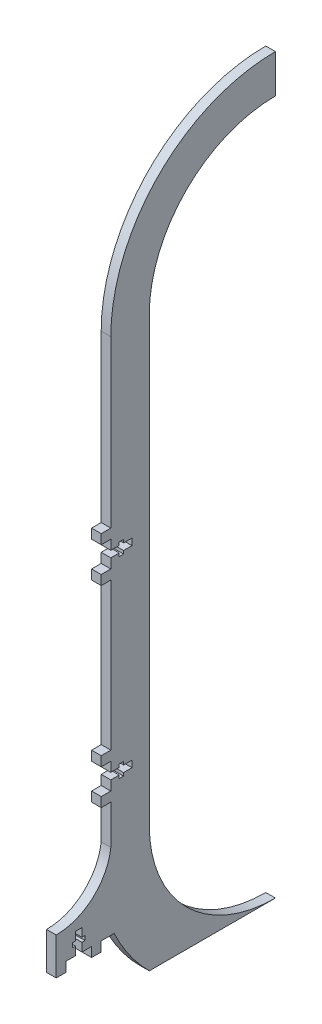
SolidWorks part; units mm, degrees
ref_plane "Front Plane" through (0, 0, 0) normal (0, 0, 1) x (1, 0, 0)
ref_plane "Top Plane" through (0, 0, 0) normal (0, 1, 0) x (1, 0, 0)
ref_plane "Right Plane" through (0, 0, 0) normal (1, 0, 0) x (0, 0, -1)
sketch "Elevator Ball Support Rail" plane through (0, 0, 0) normal (1, 0, 0) x (0, 0, -1)
  line L0 (83.312, 229.362) -> (83.312, 254.762)
  line L1 (-31.75, -120.142) -> (-25.4, -120.142)
  line L2 (83.312, -229.362) -> (0, -229.362)
  line L3 (-31.75, -196.342) -> (-23.2361, -196.342)
  line L6 (0, 146.05) -> (0, -146.05)
  line L7 (-25.4, -146.05) -> (-25.4, -196.342) construction
  line L8 (0, -146.05) -> (0, -229.362) construction
  line L12 (-61.468, -178.0893) -> (-61.468, -196.342)
  line L42 (0, 0) -> (-25.4, 0) construction
  line L46 (-25.4, 6.858) -> (-25.4, -90.424)
  line L47 (-25.4, -90.424) -> (-31.75, -90.424)
  line L48 (-25.4, -96.774) -> (-25.4, -103.124)
  line L49 (-31.75, -90.424) -> (-31.75, -96.774)
  line L50 (-31.75, -96.774) -> (-25.4, -96.774)
  line L51 (-25.4, -103.124) -> (-19.865, -103.124)
  line L52 (-19.865, -103.124) -> (-19.865, -101.083)
  line L53 (-19.865, -101.083) -> (-16.965, -101.083)
  line L54 (-16.965, -101.083) -> (-16.965, -103.124)
  line L55 (-16.965, -103.124) -> (-11.43, -103.124)
  line L56 (-11.43, -103.124) -> (-11.43, -107.442)
  line L57 (-11.43, -107.442) -> (-16.965, -107.442)
  line L58 (-16.965, -107.442) -> (-16.965, -109.483)
  line L59 (-16.965, -109.483) -> (-19.865, -109.483)
  line L60 (-19.865, -109.483) -> (-19.865, -107.442)
  line L61 (-19.865, -107.442) -> (-25.4, -107.442)
  line L62 (-25.4, -107.442) -> (-25.4, -113.792)
  line L63 (-25.4, -113.792) -> (-31.75, -113.792)
  line L64 (-31.75, -113.792) -> (-31.75, -120.142)
  line L66 (-25.4, -120.142) -> (-25.4, -146.05)
  line L68 (-25.4, 36.576) -> (-25.4, 146.05)
  arc A0 (0, 146.05) -> (83.312, 229.362) centre (83.312, 146.05) cw
  arc A1 (83.312, 254.762) -> (-25.4, 146.05) centre (83.312, 146.05) ccw
  arc A2 (0, -146.05) -> (83.312, -229.362) centre (83.312, -146.05) ccw
  arc A3 (-23.2361, -196.342) -> (0, -229.362) centre (83.312, -146.05) ccw
  arc A4 (-61.468, -178.0893) -> (-25.4, -146.05) centre (-61.468, -141.768) ccw
  point P4 (0, 0)
  line B0 (-55.118, -196.342) -> (-55.118, -202.692)
  line B1 (-55.118, -202.692) -> (-61.468, -202.692)
  line B2 (-61.468, -202.692) -> (-61.468, -196.342)
  line B3 (-48.768, -196.342) -> (-48.768, -190.807)
  line B4 (-48.768, -190.807) -> (-50.809, -190.807)
  line B5 (-50.809, -190.807) -> (-50.809, -187.907)
  line B6 (-50.809, -187.907) -> (-48.768, -187.907)
  line B7 (-48.768, -187.907) -> (-48.768, -182.372)
  line B8 (-48.768, -182.372) -> (-44.45, -182.372)
  line B9 (-44.45, -182.372) -> (-44.45, -187.907)
  line B10 (-44.45, -187.907) -> (-42.409, -187.907)
  line B11 (-42.409, -187.907) -> (-42.409, -190.807)
  line B12 (-42.409, -190.807) -> (-44.45, -190.807)
  line B13 (-44.45, -190.807) -> (-44.45, -196.342)
  line B14 (-46.609, -182.372) -> (-46.609, -196.342) construction
  line B15 (-38.1, -196.342) -> (-44.45, -196.342)
  line B16 (-31.75, -202.692) -> (-31.75, -196.342)
  line B17 (-55.118, -196.342) -> (-48.768, -196.342)
  line B18 (-38.1, -202.692) -> (-31.75, -202.692)
  line B19 (-38.1, -196.342) -> (-38.1, -202.692)
  line B20 (-25.4, 30.226) -> (-31.75, 30.226)
  line B21 (-31.75, 30.226) -> (-31.75, 36.576)
  line B22 (-31.75, 36.576) -> (-25.4, 36.576)
  line B23 (-25.4, 23.876) -> (-19.865, 23.876)
  line B24 (-19.865, 23.876) -> (-19.865, 25.917)
  line B25 (-19.865, 25.917) -> (-16.965, 25.917)
  line B26 (-16.965, 25.917) -> (-16.965, 23.876)
  line B27 (-16.965, 23.876) -> (-11.43, 23.876)
  line B28 (-11.43, 23.876) -> (-11.43, 19.558)
  line B29 (-11.43, 19.558) -> (-16.965, 19.558)
  line B30 (-16.965, 19.558) -> (-16.965, 17.517)
  line B31 (-16.965, 17.517) -> (-19.865, 17.517)
  line B32 (-19.865, 17.517) -> (-19.865, 19.558)
  line B33 (-19.865, 19.558) -> (-25.4, 19.558)
  line B34 (-11.43, 21.717) -> (-25.4, 21.717) construction
  line B35 (-25.4, 13.208) -> (-25.4, 19.558)
  line B36 (-31.75, 6.858) -> (-25.4, 6.858)
  line B37 (-25.4, 30.226) -> (-25.4, 23.876)
  line B38 (-31.75, 13.208) -> (-31.75, 6.858)
  line B39 (-25.4, 13.208) -> (-31.75, 13.208)
  dimension "D5" = 25.4
  dimension "D4" = 83.312
  dimension "D7" = 83.312
  dimension "D8" = 26.67
  dimension "D6" = 203.2
  dimension "D1" = 6.35
  dimension "D3" = 292.1
  dimension "D9" = 40.604
  dimension "D20" = 50.292
  dimension "D28" = 6.35
  dimension "D29" = 4.318
  dimension "D30" = 2.9
  dimension "D31" = 13.97
  dimension "D32" = 6.35
  dimension "D33" = 8.4
  dimension "D34" = 6.35
  dimension "D36" = 25.4
  dimension "D37" = 76.2
sketch_block_instance "Male T-slot assembly-1"
sketch_block "Male T-slot assembly" parameters "D1"=6.35, "D2"=6.35, "D3"=4.318, "D4"=2.9, "D5"=8.4, "D6"=13.97, "D7"=6.35
sketch_block_instance "Male T-slot assembly-5"
extrude "Boss-Extrude2" add sketch "Elevator Ball Support Rail" along normal blind 6.35 contours A4 L12 L3 A3 L2 A2 L6 A0 L0 A1 L46 L47 L49 L50 region at (0, -0.0213, 2.777)
equation "\"Ball Diameter\"= 1.75in"
equation "\"Pulley Diameter\" = 1in"
equation "\"Reactor Height\" = 14in"
equation "\"Sheet Thickness\"= 0.25in"
equation "\"Screw Diameter\"= .17in"
equation "\"Robot Diameter\"= 14in"
equation "\"Castor Screw Diameter\"= 0.22in"
equation "\"Wheel Diameter\" = 4in"
equation "\"Nut Diameter\" = 8.4mm"
equation "\"Nut Height\" = 2.9mm"
equation "\"Screw Height\" = 0.55in"
equation "\"D11@Elevator Ball Support Rail\"=\"Sheet Thickness\""
equation "\"Elevator Height\" = 11.5in"
equation "\"D7@Elevator Ball Support Rail\" = \"Elevator Clearance from Axis\""
equation "\"D13@Elevator Ball Support Rail\"=\"Sheet Thickness\""
equation "\"D1@T-Slot\" = \"Screw Diameter\""
equation "\"D16@Elevator Ball Support Rail\"=\"Nut Diameter\""
equation "\"D15@Elevator Ball Support Rail\"=\"Nut Height\""
equation "\"D1@Boss-Extrude2\"=\"Sheet Thickness\""
equation "\"D3@Elevator Ball Support Rail\"=\"Elevator Height\""
equation "\"Elevator Width\" = \"Ball Diameter\" + 0.25in"
equation "\"Elevator Bearing Diameter\" = sqr(2*(\"Sheet Thickness\"^2)) + 0.2in"
equation "\"Elevator Axle Endcap Diameter\" = \"Pulley Diameter\" + 0.25in"
equation "\"Elevator Axle Length\" = \"Elevator Width\" + 8*\"Sheet Thickness\""
equation "\"Elevator Clearance from Axis\" = 3.28in"
equation "\"D4@Elevator Ball Support Rail\"=\"Elevator Clearance from Axis\""
equation "\"D32@Elevator Ball Support Rail\"=\"Sheet Thickness\""
equation "\"D33@Elevator Ball Support Rail\"=\"Nut Diameter\""
equation "\"D34@Elevator Ball Support Rail\"=\"Sheet Thickness\""
equation "\"D30@Elevator Ball Support Rail\"=\"Nut Height\""
equation "\"D28@Elevator Ball Support Rail\"=\"Sheet Thickness\""
equation "\"D29@Elevator Ball Support Rail\"=\"Screw Diameter\""
equation "\"D31@Elevator Ball Support Rail\" = \"Screw Height\""
equation "\"D1@Elevator Ball Support Rail\"=\"Sheet Thickness\""
equation "\"Ball Radius\" = \"Ball Diameter\"/2"
equation "\"Elevator Horizontal Clearance\" = \"Elevator Width\" + 0.5in"
equation "\"Claw Horizontal Seperation\" = (\"Elevator Width\"/2) - (1.5 * \"Sheet Thickness\") - 0.15in"
equation "\"Claw Radius\" = \"Ball Radius\" + 0.1in"
equation "\"Castor Wheel Height\" = 1.25in"
equation "\"D8@Elevator Ball Support Rail\"=\"Castor Wheel Height\"-0.2in"
